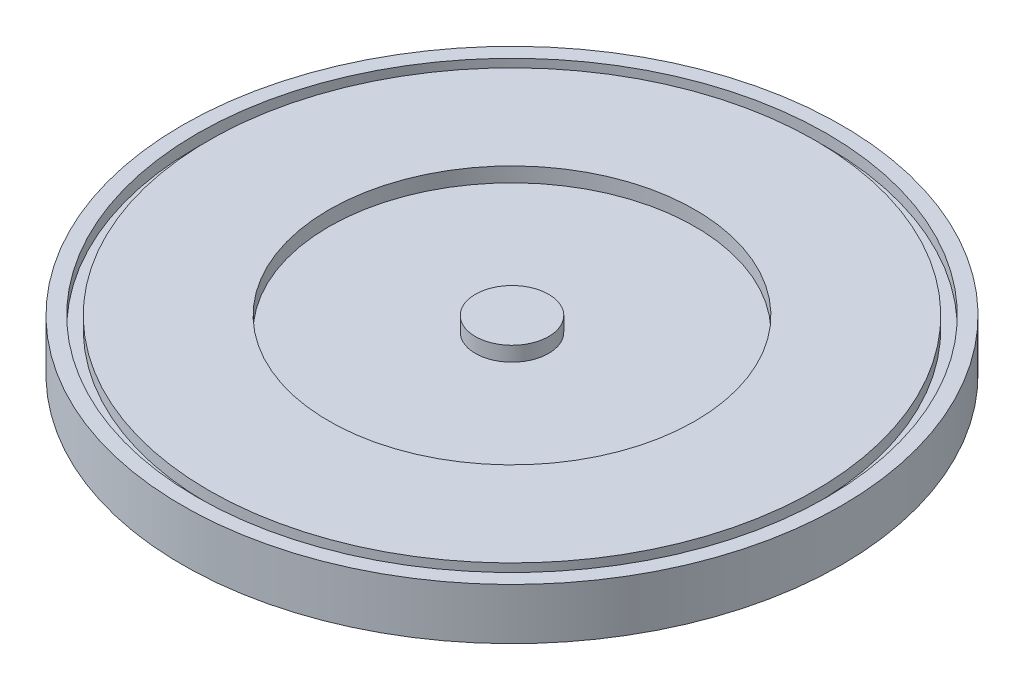
SolidWorks part; units mm, degrees
material "AISI 304"
ref_plane "Front Plane" through (0, 0, 0) normal (0, 0, 1) x (1, 0, 0)
ref_plane "Top Plane" through (0, 0, 0) normal (0, 1, 0) x (1, 0, 0)
ref_plane "Right Plane" through (0, 0, 0) normal (1, 0, 0) x (0, 0, -1)
sketch "Main Shape Profile" plane through (0, 0, 0) normal (0, 0, 1) x (1, 0, 0)
  line L1 (57.15, 0) -> (57.15, 8.89)
  line L2 (57.15, 8.89) -> (31.75, 8.89)
  line L3 (31.75, 8.89) -> (31.75, 6.35)
  line L4 (31.75, 6.35) -> (6.35, 6.35)
  line L5 (0, 8.89) -> (0, 0)
  line L6 (0, 0) -> (57.15, 0)
  line L7 (0, 0) -> (0, -50000) construction
  line L8 (0, 8.89) -> (6.35, 8.89)
  line L9 (6.35, 8.89) -> (6.35, 6.35)
  point P4 (0, 0)
  dimension "Inner Injector Diameter" = 63.5
  dimension "Kerosene Manifold Thickness" = 2.54
  dimension "Kersoene Plate Thickness" = 6.35
  dimension "Standoff Diameter" = 12.7
  dimension "Kerosene Plate Outer Diameter" = 114.3
revolve "Main Shape" add sketch "Main Shape Profile" angle 360 about L7
sketch "O Rings Profile" plane through (0, 0, 0) normal (0, 0, 1) x (1, 0, 0)
  line L0 (57.15, 8.89) -> (-57.15, 8.89) construction
  line L1 (52.578, 8.89) -> (54.61, 8.89)
  line L2 (52.578, 8.89) -> (52.578, 6.858)
  line L3 (52.578, 6.858) -> (54.61, 6.858)
  line L4 (54.61, 8.89) -> (54.61, 6.858)
  line L5 (-57.15, 0) -> (57.15, 0) construction
  line L6 (52.578, 0) -> (54.61, 0)
  line L7 (52.578, 0) -> (52.578, 2.032)
  line L8 (52.578, 2.032) -> (54.61, 2.032)
  line L9 (54.61, 0) -> (54.61, 2.032)
  line L10 (57.15, 0) -> (57.15, 8.89) construction
  line L11 (0, 0) -> (0, -50000) construction
  dimension "O Ring Depth1" = 2.032
  dimension "O Ring Width" = 2.032
  dimension "O Ring Position" = 2.54
revolve "O-Rings Cutout" cut sketch "O Rings Profile" angle 360 about L11
sketch "Sketch1" plane through (0, 8.89, 0) normal (0, 1, 0) x (1, 0, 0)
  line L0 (-37.1499, 0) -> (37.1499, 0) construction
  line L1 (-37.1499, 9.4609) -> (37.1499, 9.4609)
  line L2 (-37.1499, -9.4609) -> (37.1499, -9.4609)
  arc A0 (-37.1499, 9.4609) -> (-37.1499, -9.4609) centre (-37.1499, 0) ccw
  arc A1 (37.1499, -9.4609) -> (37.1499, 9.4609) centre (37.1499, 0) ccw
  point P2 (0, 0)
